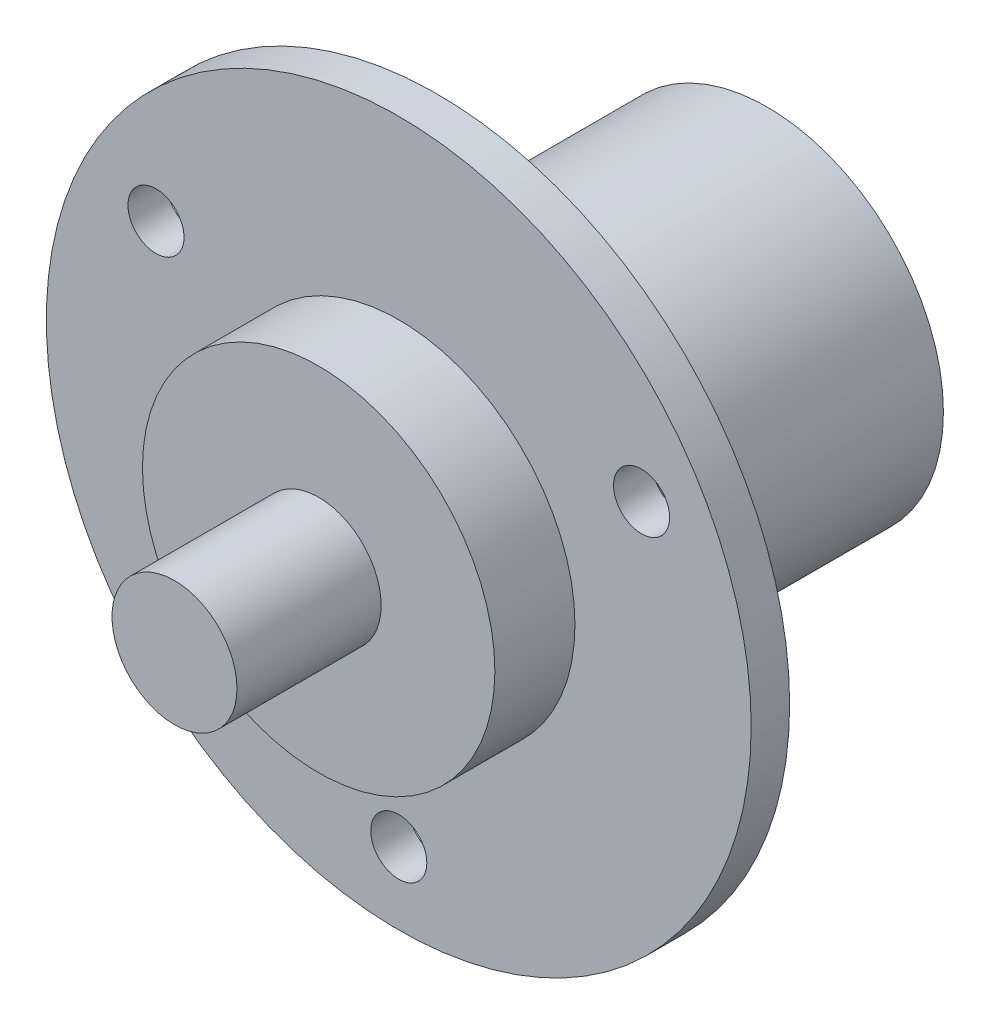
SolidWorks part; units mm, degrees
ref_plane "Plan de face" through (0, 0, 0) normal (0, 0, 1) x (1, 0, 0)
ref_plane "Plan de dessus" through (0, 0, 0) normal (0, 1, 0) x (1, 0, 0)
ref_plane "Plan de droite" through (0, 0, 0) normal (1, 0, 0) x (0, 0, -1)
sketch "Esquisse1" plane through (0, 0, 0) normal (0, 0, 1) x (1, 0, 0)
  line L0 (-15.1554, 8.75) -> (0, 0) construction
  line L1 (0, 0) -> (15.1554, 8.75) construction
  line L2 (0, 0) -> (0, -17.5) construction
  circle A0 centre (0, 0) radius 22
  circle A1 centre (0, 0) radius 17.5 construction
  circle A2 centre (-15.1554, 8.75) radius 1.75
  circle A3 centre (15.1554, 8.75) radius 1.75
  circle A4 centre (0, -17.5) radius 1.75
  circle A5 centre (0, 0) radius 11
  circle A6 centre (0, 0) radius 3.9
  dimension "D1" = 44
  dimension "D2" = 35
  dimension "D3" = 3.5
  dimension "D6" = 22
  dimension "D7" = 7.8
  dimension "D4" = 120
  dimension "D5" = 120
extrude "Boss.-Extru.1" add sketch "Esquisse1" along normal blind 2.4 contours A0
extrude "Boss.-Extru.2" add sketch "Esquisse1<3>" along normal blind 7.4 and the other way blind 20.6 contours A5
sketch "Esquisse1<3>" plane through (0, 0, 0) normal (0, 0, 1) x (1, 0, 0) same geometry as "Esquisse1"
extrude "Boss.-Extru.3" add sketch "Esquisse1<4>" along normal blind 16.4 contours A6
sketch "Esquisse1<4>" plane through (0, 0, 0) normal (0, 0, 1) x (1, 0, 0) same geometry as "Esquisse1"
extrude "Enlèv. mat.-Extru.1" cut sketch "Esquisse1<5>" along normal through all contours A3 | A2 | A4 region at (-15.1554, 8.75, 0) region at (15.1554, 8.75, 0) region at (0, -17.5, 0)
sketch "Esquisse1<5>" plane through (0, 0, 0) normal (0, 0, 1) x (1, 0, 0) same geometry as "Esquisse1"
